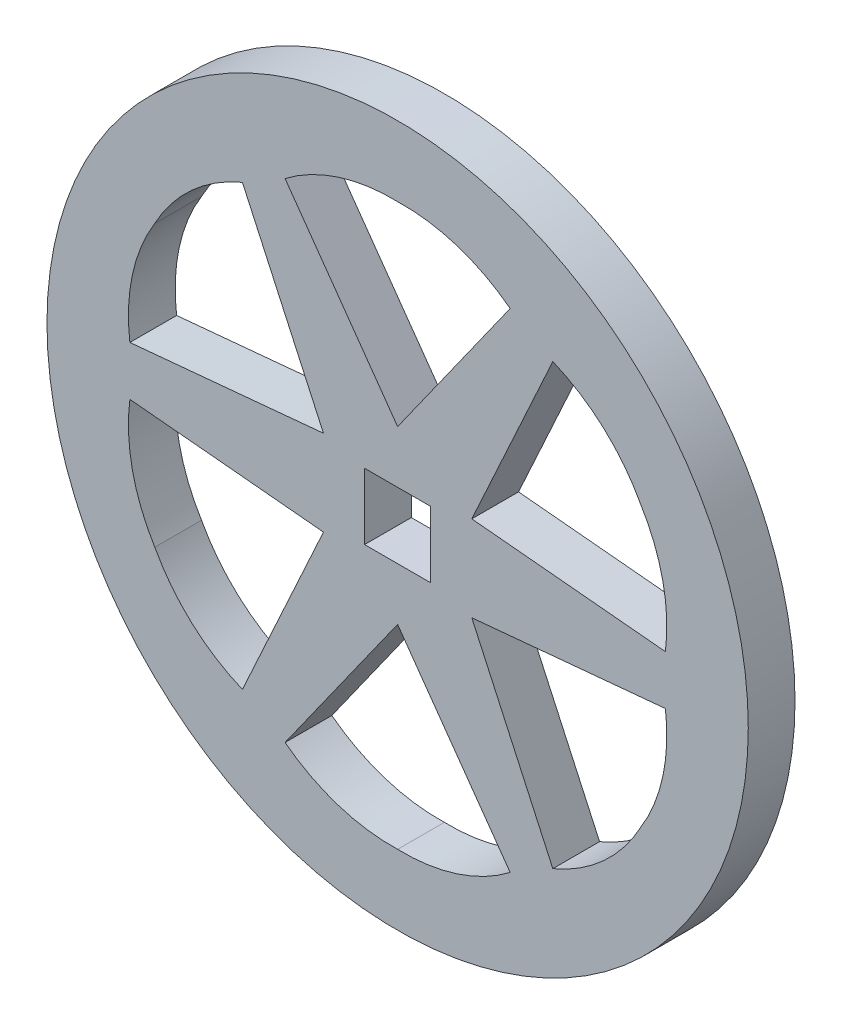
SolidWorks part; units mm, degrees
ref_plane "Front Plane" through (0, 0, 0) normal (0, 0, 1) x (1, 0, 0)
ref_plane "Top Plane" through (0, 0, 0) normal (0, 1, 0) x (1, 0, 0)
ref_plane "Right Plane" through (0, 0, 0) normal (1, 0, 0) x (0, 0, -1)
sketch "Sketch1" plane through (0, 0, 0) normal (0, 0, 1) x (1, 0, 0)
  line L1 (3.5355, -3.5355) -> (-3.5355, -3.5355)
  line L2 (3.5355, -3.5355) -> (3.5355, 3.5355)
  line L3 (3.5355, 3.5355) -> (-3.5355, 3.5355)
  line L4 (-3.5355, -3.5355) -> (-3.5355, 3.5355)
  line L5 (3.5355, -3.5355) -> (-3.5355, 3.5355) construction
  line L6 (3.5355, 3.5355) -> (-3.5355, -3.5355) construction
  circle A0 centre (0, 0) radius 37.5
  circle A1 centre (0, 0) radius 5 construction
  dimension "D1" = 75
  dimension "D2" = 10
extrude "Boss-Extrude1" add sketch "Sketch1" along normal mid plane 5
sketch "Sketch2" plane through (0, 0, 0) normal (0, 0, 1) x (1, 0, 0)
  line L0 (0, 0) -> (0, 32.5712) construction
  line L1 (0, 9.1586) -> (-12.0371, 26.1152)
  line L2 (0, 9.1586) -> (12.0371, 26.1152)
  arc A0 (-12.0371, 26.1152) -> (0, 29.9881) centre (-0.5568, 11.0765) cw
  arc A1 (12.0371, 26.1152) -> (0, 29.9881) centre (0.5568, 11.0765) ccw
extrude "Cut-Extrude1" cut sketch "Sketch2" along normal mid plane 8
pattern_circular "CirPattern1" count 6 over 360 about axis through (0, 0, 2.5) along (0, 0, -1) of "Cut-Extrude1" reverse direction yes
